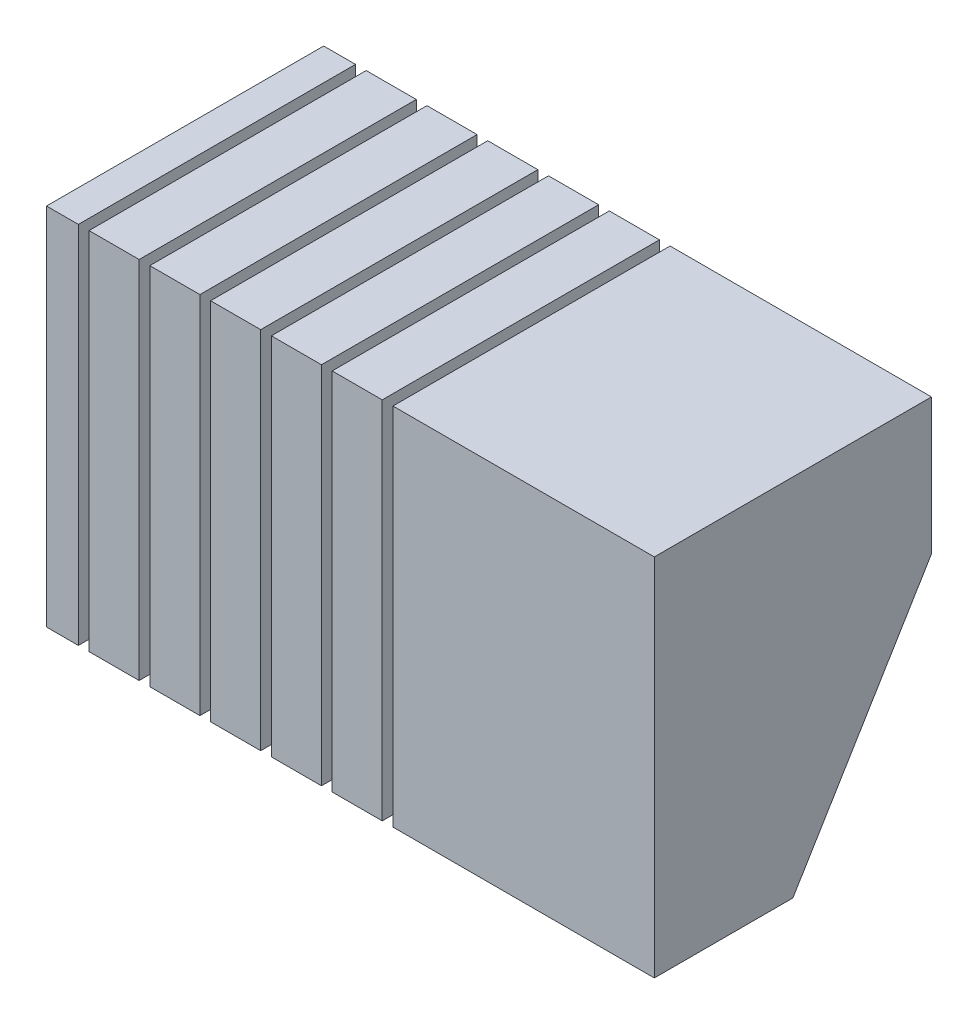
SolidWorks part; units mm, degrees
other "零件1"
other "零件7"
other "零件2"
other "复制-零件2"
other "复制-零件2-2"
other "复制-零件2-3"
other "零件3"
ref_plane "前视基准面" through (0, 0, 0) normal (0, 0, 1) x (1, 0, 0)
ref_plane "上视基准面" through (0, 0, 0) normal (0, 1, 0) x (1, 0, 0)
ref_plane "右视基准面" through (0, 0, 0) normal (1, 0, 0) x (0, 0, -1)
sketch "Sketch1" plane through (0, 0, 0) normal (0, 0, 1) x (1, 0, 0)
  line L1 (-125, -75) -> (125, -75)
  line L2 (-125, -75) -> (-125, 75)
  line L3 (-125, 75) -> (125, 75)
  line L4 (125, -75) -> (125, 75)
  line L5 (-125, -75) -> (125, 75) construction
  line L6 (-125, 75) -> (125, -75) construction
  point P0 (0, 0)
  dimension "D1" = 250
  dimension "D2" = 150
extrude "Boss-Extrude1" add sketch "Sketch1" along normal blind 114
sketch "sketchCenterLine" plane through (0, 0, 114) normal (0, 0, 1) x (1, 0, 0)
  line L0 (0, 0) -> (-160.1488, 0) construction
  line L1 (-170, 12.5) -> (-115, 12.5)
  line L2 (-97.3223, 19.8223) -> (-69.467, 47.6777)
  line L3 (-51.7893, 55) -> (70, 55)
  line L4 (95, 30) -> (95, -30)
  line L5 (70, -55) -> (-51.7893, -55)
  line L6 (-69.467, -47.6777) -> (-97.3223, -19.8223)
  line L7 (-115, -12.5) -> (-170, -12.5)
  line L8 (-125, 75) -> (-125, -75) construction
  arc A0 (70, -55) -> (95, -30) centre (70, -30) ccw
  arc A1 (95, 30) -> (70, 55) centre (70, 30) ccw
  arc A2 (-115, 12.5) -> (-97.3223, 19.8223) centre (-115, 37.5) ccw
  arc A3 (-97.3223, -19.8223) -> (-115, -12.5) centre (-115, -37.5) ccw
  arc A4 (-51.7893, -55) -> (-69.467, -47.6777) centre (-51.7893, -30) cw
  arc A5 (-69.467, 47.6777) -> (-51.7893, 55) centre (-51.7893, 30) cw
  point P24 (-62.1447, -55)
  point P27 (-62.1447, 55)
  dimension "D1" = 25
  dimension "D2" = 25
  dimension "D8" = 10
  dimension "D3" = 95
  dimension "D4" = 110
  dimension "D5" = 25
  dimension "D6" = 45
  dimension "D7" = 45
sketch3d "3DSketch1"
  line L0 (125, -75, 114) -> (125, -75, 0) construction
  line L1 (125, -75, 0) -> (125, 75, 0) construction
  line L2 (-125, -75, 0) -> (125, -75, 0) construction
  point P0 (125, -75, 57)
  point P1 (125, 19.0618, 0)
  point P4 (42.2925, -75, 0)
ref_plane "Plane1" through (27.9069, -24.5383, -40.4932) normal (-0.5078, 0.4465, 0.7368) x (0.8615, 0.2632, 0.4343)
sketch "Sketch4" plane through (27.9069, -24.5383, -40.4932) normal (-0.5078, 0.4465, 0.7368) x (0.8615, 0.2632, 0.4343)
  line L1 (-16.3307, -143.8321) -> (142.4953, -143.8321)
  line L2 (-16.3307, -143.8321) -> (-16.3307, 25.2667)
  line L3 (-16.3307, 25.2667) -> (142.4953, 25.2667)
  line L4 (142.4953, -143.8321) -> (142.4953, 25.2667)
extrude "Cut-Extrude1" cut sketch "Sketch4" against normal blind 114
sketch "Sketch5" plane through (0, -75, 0) normal (0, -1, 0) x (1, 0, 0)
  line L1 (-111.911, -16.0572) -> (-107.5129, -16.0572)
  line L2 (-111.911, -16.0572) -> (-111.911, 130.5458)
  line L3 (-111.911, 130.5458) -> (-107.5129, 130.5458)
  line L4 (-107.5129, -16.0572) -> (-107.5129, 130.5458)
extrude "Cut-Extrude2" cut sketch "Sketch5" against normal through all
pattern_linear "LPattern1" count 6 spacing 25 along (1, 0, 0) of "Cut-Extrude2"
